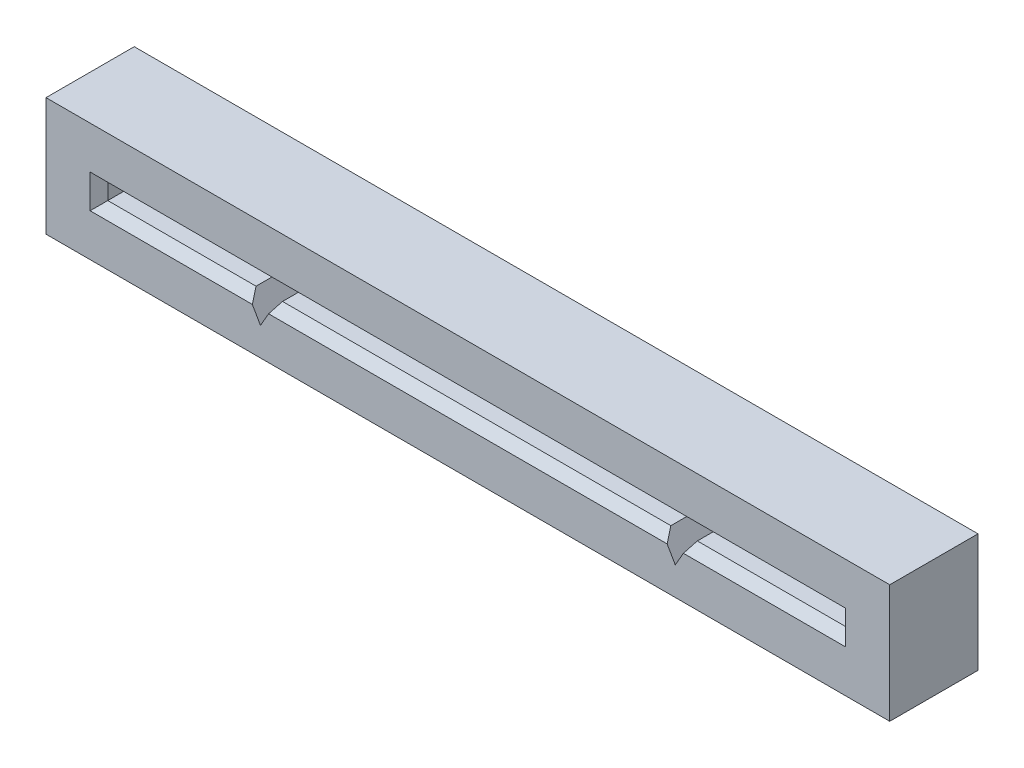
SolidWorks part; units mm, degrees
material "Сосна"
ref_plane "Front" through (0, 0, 0) normal (0, 0, 1) x (1, 0, 0)
ref_plane "Top" through (0, 0, 0) normal (0, 1, 0) x (1, 0, 0)
ref_plane "Right" through (0, 0, 0) normal (1, 0, 0) x (0, 0, -1)
sketch "Эскиз1" plane through (0, 66.7543, 0) normal (0, 0, 1) x (-1, 0, 0)
  line L1 (23.9, 63.4043) -> (-23.9, 70.1043) construction
  line L31 (-23.9, 63.4043) -> (23.9, 63.4043)
  line L32 (-23.9, 63.4043) -> (-23.9, 70.1043)
  line L33 (-23.9, 70.1043) -> (23.9, 70.1043)
  line L34 (23.9, 63.4043) -> (23.9, 70.1043)
  line L35 (-23.9, 63.4043) -> (23.9, 70.1043) construction
  point P12 (0, 66.7543)
  point P22 (0, 66.7543)
  point P26 (0, 66.7543)
  dimension "D1" = 6.7
  dimension "D2" = 47.8
extrude "Бобышка-Вытянуть1" add sketch "Эскиз1" along normal blind 5
sketch "Эскиз2" plane through (0, 66.7543, 5) normal (0, 0, 1) x (-1, 0, 0)
  line L1 (20.9, 67.2043) -> (20.9, 70.1043) construction
  line L4 (-20.9, 67.2043) -> (-20.9, 66.3043)
  line L5 (-20.9, 66.3043) -> (20.9, 66.3043)
  line L6 (20.9, 67.2043) -> (20.9, 66.3043)
  line L7 (-20.9, 67.2043) -> (20.9, 66.3043) construction
  line L8 (-20.9, 66.3043) -> (20.9, 67.2043) construction
  line L22 (20.9, 67.2043) -> (-20.9, 67.2043) construction
  line L23 (0, 66.3043) -> (0, 67.2043) construction
  line L24 (-20.9, 67.2043) -> (-12.5, 67.2043)
  line L25 (-12.5, 67.2043) -> (-11.75, 68.5043)
  line L26 (-11.75, 68.5043) -> (-11, 67.2043)
  line L27 (-11, 67.2043) -> (11, 67.2043)
  line L28 (11, 67.2043) -> (11.75, 68.5043)
  line L29 (11.75, 68.5043) -> (12.5, 67.2043)
  line L30 (12.5, 67.2043) -> (20.9, 67.2043)
  line L31 (23.9, 70.1043) -> (-23.9, 70.1043) construction
  line L33 (-20.9, 66.3043) -> (-20.9, 63.4043) construction
  line L34 (-23.9, 63.4043) -> (23.9, 63.4043) construction
  point P6 (0, 66.7543)
  point P12 (0, 66.7543)
  point P14 (0, 67.2043)
  point P15 (0, 66.7543)
  point P16 (-11.8362, 67.8593)
  point P20 (-20.7482, 65.0952)
  point P22 (0, 66.7543)
  point P25 (-20.9018, 67.2592)
  dimension "D1" = 41.8
  dimension "D2" = 0.9
  dimension "D3" = 1.3
  dimension "D4" = 23.5
  dimension "D5" = 1.5
extrude "Вырез-Вытянуть1" cut sketch "Эскиз2" against normal through all and the other way through all
chamfer "Фаска1" distance 0.5 angle 45 6 edges at (16.7, -0.45, 5) (20.9, 0, 5) (0, 0.45, 5) (-20.9, 0, 5) (-16.7, -0.45, 5) (0, -0.45, 5)
